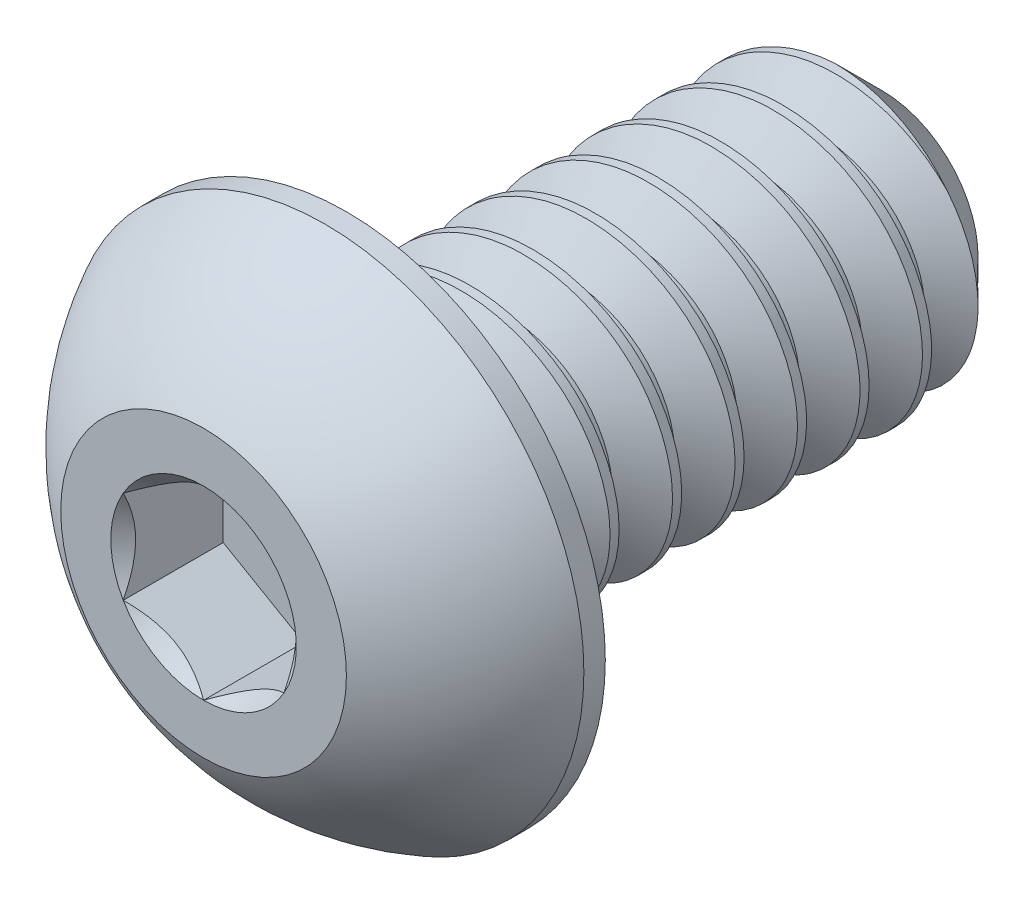
SolidWorks part; units mm, degrees
ref_plane "Front" through (0, 0, 0) normal (0, 0, 1) x (1, 0, 0)
ref_plane "Top" through (0, 0, 0) normal (0, 1, 0) x (1, 0, 0)
ref_plane "Right" through (0, 0, 0) normal (1, 0, 0) x (0, 0, -1)
sketch "Sketch1" plane through (0, 0, 0) normal (1, 0, 0) x (0, 0, -1)
  line L2 (0.8, 0.8) -> (3.8, 0.8)
  line L3 (3.8, 0.8) -> (3.8, 0)
  line L4 (3.8, 0) -> (0.8, 0)
  line L6 (0.68, 1.45) -> (0.8, 1.45) construction
  line L7 (3.8, 0.8) -> (3.8, -0.8) construction
  line L8 (0, 0) -> (0.8, 0) construction
  line L9 (0.8, 1.45) -> (0.8, -1.45) construction
  line L11 (0.8, 0.8) -> (0.8, 0)
  line L13 (0, 0.45) -> (0, -0.45) construction
  line L14 (0, 0.45) -> (0, 0.8) construction
  arc A3 (0, 0.8) -> (0.68, 1.45) centre (1.4154, 0) cw construction
  dimension "D1" = 0.12
  dimension "Head Ht" = 0.8
  dimension "Head Dia" = 2.9
  dimension "Dia" = 1.6
  dimension "Lg" = 3
  dimension "Hex" = 0.9
revolve "Revolve1" add sketch "Sketch1" angle 360 mid plane about L4
sketch "Sketch3" plane through (0, 0, -3.8) normal (0, 0, -1) x (-1, 0, 0)
  circle A0 centre (0, 0) radius 0.8
curve "Helix/Spiral1" pitch 0.35 height 3.35 radius 0.8 centre (0, 0, -3.8) axis (0, 0, 1) start towards (0, 1, 0)
chamfer "Chamfer1" distance 0.2625 angle 45 1 edges at (0, 0.8, -3.8)
sketch "Sketch7" plane through (0, 0, 0) normal (1, 0, 0) x (0, 0, -1)
  line L6 (0.68, 1.45) -> (0.8, 1.45) construction
  line L8 (0, 0) -> (0.8, 0) construction
  line L11 (0.8, 1.45) -> (0.8, -1.45) construction
  line L12 (0.68, 1.45) -> (0.8, 1.45)
  line L13 (0, 0) -> (0.8, 0)
  line L14 (0, 0.45) -> (0, -0.45) construction
  line L15 (0.8, 1.45) -> (0.8, 0)
  line L16 (0, 0.8) -> (0, 0)
  arc A2 (0.68, 1.45) -> (0, 0.8) centre (1.4154, 0) ccw construction
  arc A3 (0.68, 1.45) -> (0, 0.8) centre (1.4154, 0) ccw
revolve "Revolve2" add sketch "Sketch7" angle 360 mid plane about L13
sketch "Sketch5" plane through (0, 0, 0) normal (0, 0, 1) x (1, 0, 0)
  line L1 (0.45, -0.2598) -> (0.45, 0.2598)
  line L2 (0.45, 0.2598) -> (0, 0.5196)
  line L3 (0, 0.5196) -> (-0.45, 0.2598)
  line L4 (-0.45, 0.2598) -> (-0.45, -0.2598)
  line L5 (-0.45, -0.2598) -> (0, -0.5196)
  line L6 (0, -0.5196) -> (0.45, -0.2598)
  circle A0 centre (0, 0) radius 0.45 construction
extrude "Cut-Extrude2" cut sketch "Sketch5" against normal blind 0.56
sketch "Sketch6" plane through (0, 0, 0) normal (0, 0, 1) x (1, 0, 0)
  circle A0 centre (0, 0) radius 0.5196
extrude "Cut-Extrude3" cut sketch "Sketch6" against normal blind 0.56 draft 45
sketch "Sketch2" plane through (0, 0, 0) normal (1, 0, 0) x (0, 0, -1)
  line L0 (3.5375, 0.8) -> (3.8367, 0.8)
  line L1 (3.8367, 0.8) -> (3.7125, 0.5848)
  line L2 (3.7125, 0.5848) -> (3.6617, 0.5848)
  line L3 (3.6617, 0.5848) -> (3.5375, 0.8)
  line L4 (3.5996, 0.6924) -> (3.7746, 0.6924) construction
  dimension "D1" = 60
  dimension "D2" = 0.0508
  dimension "D3" = 0.175
sweep "Cut-Sweep1" cut profiles "Sketch2" path "Helix/Spiral1"
ref_axis "Center Axis 1" through (0, 0, -4.0296) along (0, 0, 1)
ref_plane "Contact Plane 1" through (0, 0, -0.8) normal (0, 0, -1) x (-1, 0, 0)
ref_plane "Contact Plane 2" through (0, 0, 0) normal (0, 0, 1) x (1, 0, 0)
equation "\"D3@Helix/Spiral1\" = \"Lg@Sketch1\" + \"D4@Helix/Spiral1\""
equation "\"D2@Sketch2\"=\"D4@Helix/Spiral1\" * .145"
equation "\"D3@Sketch2\" = \"D4@Helix/Spiral1\" * .5"
equation "\"D1@Chamfer1\" = \"D4@Helix/Spiral1\" * .75"
equation "\"D1@Cut-Extrude2\" = \"Head Ht@Sketch1\" * .7"
equation "\"D1@Sketch1\" = \"Head Ht@Sketch1\" * .15"
equation "\"D1@Cut-Extrude3\" = \"D1@Cut-Extrude2\""
